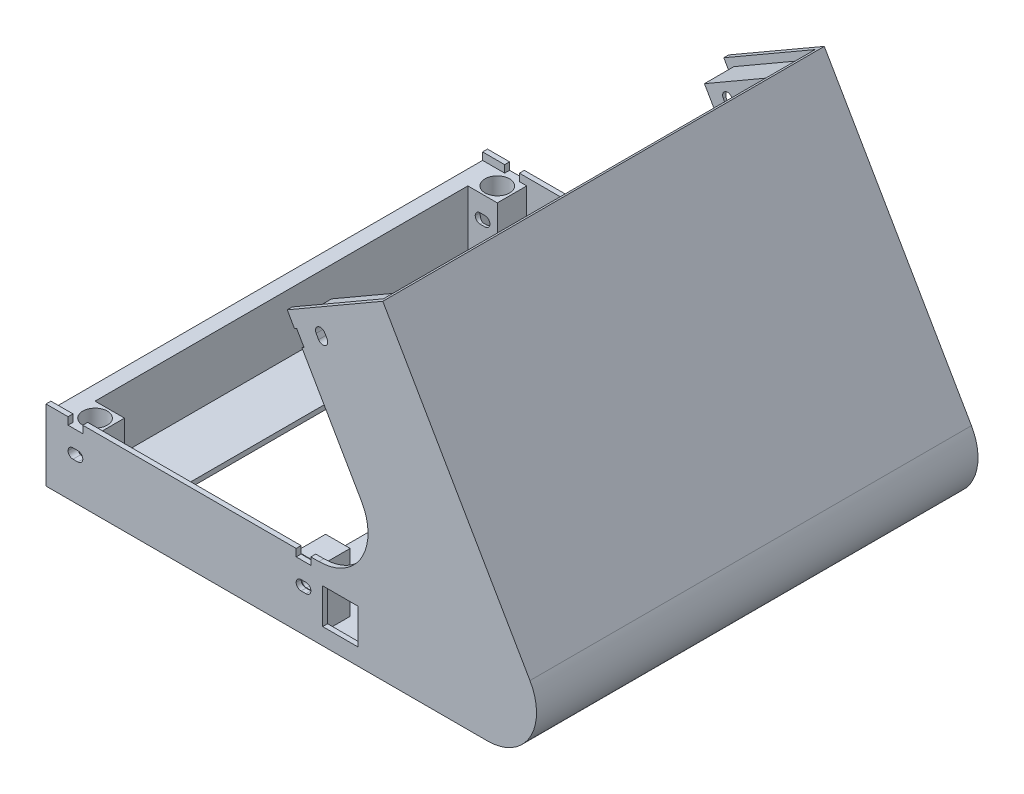
SolidWorks part; units mm, degrees
ref_plane "Płaszczyzna przednia" through (0, 0, 0) normal (0, 0, 1) x (1, 0, 0)
ref_plane "Płaszczyzna górna" through (0, 0, 0) normal (0, 1, 0) x (1, 0, 0)
ref_plane "Płaszczyzna prawa" through (0, 0, 0) normal (1, 0, 0) x (0, 0, -1)
sketch "Szkic1" plane through (0, 0, 0) normal (0, 0, 1) x (1, 0, 0)
  line L0 (-53.9898, 0) -> (36.0102, 0)
  line L1 (44.6705, 15) -> (14.6705, 66.9615)
  line L2 (-53.9898, 1) -> (36.0102, 1)
  line L3 (43.8045, 14.5) -> (13.8045, 66.4615)
  line L4 (-53.9898, 1) -> (-53.9898, 0)
  line L5 (14.6705, 66.9615) -> (13.8045, 66.4615)
  arc A0 (36.0102, 0) -> (44.6705, 15) centre (36.0102, 10) ccw
  arc A1 (36.0102, 1) -> (43.8045, 14.5) centre (36.0102, 10) ccw
  dimension "D2" = 10
  dimension "D1" = 60
  dimension "D3" = 90
  dimension "D4" = 60
  dimension "D5" = 1
extrude "FrontPlate" add sketch "Szkic1" along normal blind 90
sketch "Szkic2" plane through (0, 1, 0) normal (0, 1, 0) x (1, 0, 0)
  line L0 (-53.9898, -90) -> (-53.9898, 0) construction
  line L1 (-11.9898, -9.5) -> (-38.9898, -9.5)
  line L2 (-11.9898, -9.5) -> (-11.9898, -80.5)
  line L3 (-11.9898, -80.5) -> (-38.9898, -80.5)
  line L4 (-38.9898, -9.5) -> (-38.9898, -80.5)
  line L5 (-11.9898, -9.5) -> (-38.9898, -80.5) construction
  line L6 (-11.9898, -80.5) -> (-38.9898, -9.5) construction
  point P0 (-25.4898, -45)
  point P8 (-53.9898, -45)
  dimension "D1" = 27
  dimension "D2" = 71
  dimension "D3" = 15
extrude "Screen_hd44780" cut sketch "Szkic2" against normal through all
sketch "Szkic3" plane through (0, 1, 0) normal (0, 1, 0) x (1, 0, 0)
  line L0 (-53.9898, -45) -> (65.0466, -45) construction
  line L1 (-50.9898, -1) -> (-44.9898, -1)
  line L2 (-50.9898, -1) -> (-50.9898, -7)
  line L3 (-50.9898, -7) -> (-44.9898, -7)
  line L4 (-44.9898, -1) -> (-44.9898, -7)
  line L5 (-53.9898, -90) -> (-53.9898, 0) construction
  line L6 (36.0102, 0) -> (-53.9898, 0) construction
  line L7 (-44.9898, -89) -> (-44.9898, -83)
  line L8 (-50.9898, -83) -> (-44.9898, -83)
  line L9 (-50.9898, -89) -> (-50.9898, -83)
  line L10 (-50.9898, -89) -> (-44.9898, -89)
  line L11 (1.0102, -88.9) -> (1.0102, -83)
  line L12 (-3.9898, -1.1) -> (1.0102, -1.1)
  line L13 (-3.9898, -1.1) -> (-3.9898, -7)
  line L14 (-3.9898, -7) -> (1.0102, -7)
  line L15 (1.0102, -1.1) -> (1.0102, -7)
  line L20 (-3.9898, -83) -> (1.0102, -83)
  line L21 (-3.9898, -88.9) -> (-3.9898, -83)
  line L22 (-3.9898, -88.9) -> (1.0102, -88.9)
  dimension "D1" = 1
  dimension "D2" = 3
  dimension "D3" = 6
  dimension "D4" = 6
  dimension "D5" = 50
  dimension "D6" = 5
extrude "MountingPoints" add sketch "Szkic3" along normal blind 12
sketch "Szkic4" plane through (0, 13, 0) normal (0, 1, 0) x (1, 0, 0)
  line L0 (-50.9898, -1) -> (-50.9898, -7) construction
  line L2 (-44.9898, -1) -> (-50.9898, -1) construction
  line L3 (-53.9898, -45) -> (78.5439, -45) construction
  line L4 (-53.9898, -90) -> (-53.9898, 0) construction
  circle A0 centre (-47.9898, -4) radius 2.5
  circle A1 centre (-47.9898, -86) radius 2.5
  point P0 (-47.9898, -4)
  point P4 (-50.9898, -4)
  point P5 (-47.9898, -86)
  point P8 (-47.9898, -1)
  dimension "D1" = 5
extrude "Wytnij-wyciągnięcie2" cut sketch "Szkic4" against normal blind 10
sketch "Szkic5" plane through (0, 0, 90) normal (0, 0, 1) x (1, 0, 0)
  line L4 (-53.9898, 1) -> (-53.9898, 14.5)
  line L5 (13.8045, 66.4615) -> (-4.8151, 55.7115)
  line L7 (36.0102, 1) -> (-53.9898, 1) construction
  line L8 (43.8045, 14.5) -> (13.8045, 66.4615)
  line L9 (-4.8151, 55.7115) -> (10.3181, 29.5)
  line L10 (-53.9898, 14.5) -> (1.6579, 14.5)
  line L17 (36.0102, 1) -> (-53.9898, 1)
  arc A0 (36.0102, 1) -> (43.8045, 14.5) centre (36.0102, 10) ccw construction
  arc A2 (10.3181, 29.5) -> (1.6579, 14.5) centre (1.6579, 24.5) cw
  arc A5 (36.0102, 1) -> (43.8045, 14.5) centre (36.0102, 10) ccw
  dimension "D3" = 10
  dimension "D2" = 21.5
  dimension "D1" = 13.5
extrude "Dodanie-wyciągnięcie3" add sketch "Szkic5" against normal blind 1 separate body
sketch "Szkic6" plane through (0, 1, 0) normal (0, 1, 0) x (1, 0, 0)
  line L0 (36.0102, -90) -> (-53.9898, -90) construction
  line L1 (-53.9898, 0) -> (-50.9898, 0)
  line L2 (-53.9898, 0) -> (-53.9898, -90)
  line L3 (-53.9898, -90) -> (-50.9898, -90)
  line L4 (-50.9898, 0) -> (-50.9898, -90)
  line L5 (-50.9898, -83) -> (-50.9898, -89) construction
extrude "Dodanie-wyciągnięcie4" add sketch "Szkic6" along normal blind 12
pattern_linear "Szyk liniowy1" count 2 spacing 89 along (0, 0, -1) of "Dodanie-wyciągnięcie3"
sketch "Szkic7" plane through (0, 0, 90) normal (0, 0, 1) x (1, 0, 0)
  line L1 (-49.4898, 9.5) -> (-46.4898, 9.5)
  line L2 (-49.4898, 9.5) -> (-49.4898, 7.5)
  line L3 (-49.4898, 7.5) -> (-46.4898, 7.5)
  line L4 (-46.4898, 9.5) -> (-46.4898, 7.5)
  line L5 (-49.4898, 14.5) -> (-46.4898, 14.5)
  line L6 (-53.9898, 13) -> (-53.9898, 0) construction
  line L7 (1.6579, 14.5) -> (-53.9898, 14.5) construction
  line L8 (-49.4898, 14.5) -> (-49.4898, 13)
  line L9 (-2.9898, 7.5) -> (0.0102, 7.5)
  line L10 (-2.9898, 7.5) -> (-2.9898, 9.5)
  line L11 (-2.9898, 9.5) -> (0.0102, 9.5)
  line L12 (0.0102, 7.5) -> (0.0102, 9.5)
  line L13 (-49.4898, 13) -> (-46.4898, 13)
  line L14 (-46.4898, 14.5) -> (-46.4898, 13)
  line L15 (-2.9898, 14.5) -> (0.0102, 14.5)
  line L16 (-2.9898, 14.5) -> (-2.9898, 13)
  line L17 (-2.9898, 13) -> (0.0102, 13)
  line L18 (0.0102, 14.5) -> (0.0102, 13)
  dimension "D1" = 3
  dimension "D2" = 4.5
  dimension "D3" = 5
  dimension "D4" = 2
  dimension "D5" = 1.5
  dimension "D6" = 51
extrude "Wytnij-wyciągnięcie3" cut sketch "Szkic7" against normal through all both and the other way through all
sketch "Szkic8" plane through (39.132, 22.5929, 0) normal (-0.866, -0.5, 0) x (0, 0, 1)
  line L1 (89, 49.1551) -> (83, 49.1551)
  line L2 (89, 49.1551) -> (89, 43.1551)
  line L3 (89, 43.1551) -> (83, 43.1551)
  line L4 (83, 49.1551) -> (83, 43.1551)
  line L5 (90, 50.6551) -> (0, 50.6551) construction
  line L7 (89, 50.6551) -> (89, 20.3887) construction
  line L8 (45, 50.6551) -> (45, -25.1565) construction
  line L13 (7, 49.1551) -> (7, 43.1551)
  line L14 (1, 43.1551) -> (7, 43.1551)
  line L15 (1, 49.1551) -> (1, 43.1551)
  line L16 (1, 49.1551) -> (7, 49.1551)
  circle A0 centre (86, 46.1551) radius 2.5
  circle A1 centre (4, 46.1551) radius 2.5
  point P20 (89, 46.1551)
  point P21 (86, 43.1551)
  dimension "D4" = 5
  dimension "D1" = 6
  dimension "D2" = 6
  dimension "D3" = 1.5
extrude "MountingPoints2" add sketch "Szkic8" along normal blind 20
sketch "Szkic9" plane through (0, 0, 0) normal (0, 0, -1) x (-1, 0, 0)
  line L0 (-0.582, 55.3634) -> (-2.3141, 56.3634)
  line L1 (-0.582, 55.3634) -> (-2.082, 52.7654)
  line L2 (-2.3141, 56.3634) -> (-3.8141, 53.7654)
  line L3 (-2.082, 52.7654) -> (-3.8141, 53.7654)
  line L4 (-0.2339, 49.9663) -> (2.7661, 55.1625) construction
  line L6 (2.7661, 55.1625) -> (-0.2339, 49.9663) construction
  dimension "D1" = 2
  dimension "D2" = 3
  dimension "D3" = 3
  dimension "D4" = 3
extrude "Wytnij-wyciągnięcie4" cut sketch "Szkic9" against normal through all both and the other way through all
sketch "Szkic10" plane through (0, 0, 0) normal (0, 0, -1) x (-1, 0, 0)
  line L0 (3.3151, 53.1134) -> (2.8821, 53.3634)
  line L1 (3.3151, 53.1134) -> (1.8151, 50.5154)
  line L2 (2.8821, 53.3634) -> (1.3821, 50.7654)
  line L3 (1.8151, 50.5154) -> (1.3821, 50.7654)
  line L4 (4.8151, 55.7115) -> (-10.3181, 29.5) construction
  line L5 (-2.082, 52.7654) -> (-3.8141, 53.7654) construction
  line L6 (-2.3141, 56.3634) -> (-0.582, 55.3634) construction
  dimension "D1" = 0.5
extrude "Wytnij-wyciągnięcie5" cut sketch "Szkic10" against normal through all both and the other way through all
sketch "Szkic11" plane through (0, 0, 89) normal (0, 0, -1) x (-1, 0, 0)
  line L1 (-2.4102, 10.6) -> (-9.6102, 10.6)
  line L2 (-2.4102, 10.6) -> (-2.4102, 3.4)
  line L3 (-2.4102, 3.4) -> (-9.6102, 3.4)
  line L4 (-9.6102, 10.6) -> (-9.6102, 3.4)
  line L7 (-36.0102, 1) -> (44.9898, 1) construction
  line L9 (-1.0102, 13) -> (-1.0102, 1) construction
  dimension "D1" = 7.2
  dimension "D2" = 7.2
  dimension "D3" = 2.4
  dimension "D4" = 1.4
extrude "Wytnij-wyciągnięcie6" cut sketch "Szkic11" against normal blind 20
sketch "Szkic12" plane through (0, 0, 83) normal (0, 0, -1) x (-1, 0, 0)
  line L1 (-0.2339, 49.9663) -> (-17.5545, 59.9663)
  line L2 (-0.2339, 49.9663) -> (-17.5545, 59.9663) construction
  line L6 (-17.5545, 59.9663) -> (-43.8045, 14.5)
  line L7 (-17.5545, 59.9663) -> (-14.5545, 65.1625) construction
  line L8 (-0.2339, 49.9663) -> (-36.0102, 1)
  arc A1 (-43.8045, 14.5) -> (-36.0102, 1) centre (-36.0102, 10) ccw construction
  arc A2 (-43.8045, 14.5) -> (-36.0102, 1) centre (-36.0102, 10) ccw
extrude "Dodanie-wyciągnięcie6" add sketch "Szkic12" against normal up to next
ref_plane "Płaszczyzna2" through (0, 0, 45) normal (0, 0, 1) x (1, 0, 0)
mirror "Lustro2" about plane through (0, 0, 45) normal (0, 0, 1) of "Dodanie-wyciągnięcie6"
fillet "Zaokrąglenie1" radius 1 48 edges at (-2.9898, 7.5, 0.5) (-2.9898, 7.5, 4.05) (-2.9898, 9.5, 4.05) (-2.9898, 9.5, 0.5) (0.0102, 9.5, 0.5) (0.0102, 9.5, 4.05) (0.0102, 7.5, 0.5) (0.0102, 7.5, 4.05) (-2.9898, 9.5, 85.95) (-2.9898, 7.5, 85.95) (0.0102, 7.5, 85.95) (0.0102, 9.5, 85.95) (0.0102, 7.5, 89.5) (0.0102, 9.5, 89.5) (-2.9898, 9.5, 89.5) (-2.9898, 7.5, 89.5) (2.082, 52.7654, 89) (3.8141, 53.7654, 89) (2.3141, 56.3634, 89) (2.3141, 56.3634, 83.5) (0.582, 55.3634, 83.5) (0.582, 55.3634, 89) (3.8141, 53.7654, 83.5) (2.082, 52.7654, 83.5) (0.582, 55.3634, 6.5) (2.3141, 56.3634, 6.5) (2.082, 52.7654, 6.5) (3.8141, 53.7654, 6.5) (2.082, 52.7654, 1) (0.582, 55.3634, 1) (2.3141, 56.3634, 1) (3.8141, 53.7654, 1) (-49.4898, 7.5, 89) (-49.4898, 7.5, 83.5) (-49.4898, 9.5, 89) (-49.4898, 9.5, 83.5) (-46.4898, 9.5, 89) (-46.4898, 9.5, 83.5) (-46.4898, 7.5, 83.5) (-46.4898, 7.5, 89) (-46.4898, 9.5, 1) (-46.4898, 9.5, 6.5) (-49.4898, 9.5, 6.5) (-49.4898, 9.5, 1) (-49.4898, 7.5, 6.5) (-46.4898, 7.5, 6.5) (-46.4898, 7.5, 1) (-49.4898, 7.5, 1)
